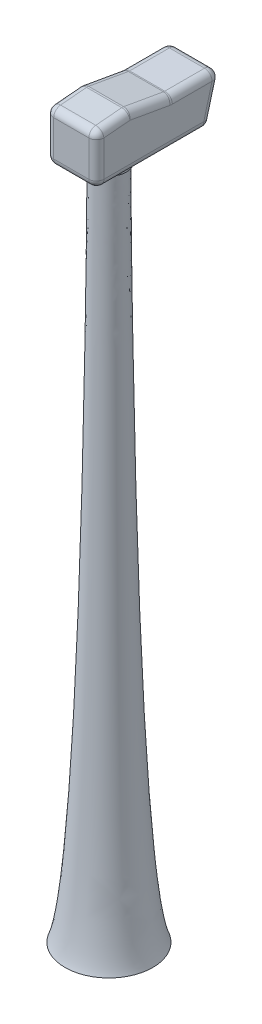
SolidWorks part; units mm, degrees
ref_plane "Ebene vorne" through (0, 0, 0) normal (0, 0, 1) x (1, 0, 0)
ref_plane "Ebene oben" through (0, 0, 0) normal (0, 1, 0) x (1, 0, 0)
ref_plane "Ebene rechts" through (0, 0, 0) normal (1, 0, 0) x (0, 0, -1)
sketch "Skizze2" plane through (0, 0, 0) normal (1, 0, 0) x (0, 0, -1)
  line L0 (2800, -4800) -> (2800, 4800)
  line L1 (-2800, -2400) -> (2800, -2400) construction
  line L2 (-2800, -2400) -> (-2800, 2400) construction
  line L3 (-2800, 2400) -> (2800, 2400) construction
  line L4 (2800, -2400) -> (2800, 2400) construction
  line L5 (-2800, -2400) -> (2800, 2400) construction
  line L6 (-2800, 2400) -> (2800, -2400) construction
  line L7 (2800, 4800) -> (9280, 5366.9265)
  line L8 (9280, 5366.9265) -> (17200, 3970.4169)
  line L9 (17200, 3970.4169) -> (26800, 3970.4169)
  line L10 (26800, 3970.4169) -> (24449.9739, -4800)
  line L11 (24449.9739, -4800) -> (2800, -4800)
  point P0 (0, 0)
  dimension "D1" = 5600
  dimension "D2" = 4800
  dimension "D3" = 95
  dimension "D4" = 165
  dimension "D5" = 75
  dimension "D6" = 6480
  dimension "D7" = 7920
  dimension "D8" = 24000
  dimension "D9" = 2400
  dimension "D10" = 2400
extrude "Aufsatz-Linear austragen1" add sketch "Skizze2" along normal blind 4800 and the other way blind 4800
fillet "Verrundung1" radius 1440 18 edges at (0, -4800, -24449.9739) (-4800, -414.7916, -25624.9869) (-4800, -4800, -13624.9869) (-4800, 0, -2800) (0, -4800, -2800) (4800, 0, -2800) (4800, -414.7916, -25624.9869) (4800, -4800, -13624.9869) (-4800, 3970.4169, -22000) (0, 3970.4169, -26800) (4800, 3970.4169, -22000) (-4800, 4668.6717, -13240) (0, 3970.4169, -17200) (4800, 4668.6717, -13240) (-4800, 5083.4633, -6040) (0, 5366.9265, -9280) (4800, 5083.4633, -6040) (0, 4800, -2800)
sketch "Skizze3" plane through (0, 0, 0) normal (1, 0, 0) x (0, 0, -1)
  line L0 (10000, 0) -> (10000, -215.2925) construction
  line L1 (10000, -3360) -> (6640, -3360)
  line L2 (4240, -3360) -> (23345.023, -3360) construction
  line L3 (6640, -3360) -> (6640, -5760)
  line L4 (6640, -5760) -> (6880, -5760)
  line L5 (6880, -5760) -> (6880, -4800)
  line L6 (23345.023, -4800) -> (4240, -4800) construction
  line L7 (6880, -4800) -> (7024, -4800)
  line L8 (7024, -4800) -> (7024, -5760)
  line L9 (10000, -3360) -> (10000, -135000)
  line L10 (1600, -135000) -> (10000, -135000)
  line L11 (-37.4147, 0) -> (55.262, 0) construction
  line L13 (2800, -3360) -> (2800, 3480.4831) construction
  line L14 (6640, -5760) -> (161.2362, -5760) construction
  spline S0 degree 3 poles (7024, -5760) (7024, -6115.3967) (6652.6696, -122885.6955) (1600, -135000) knots 0 0 0 0 1 1 1 1
  dimension "D1" = 2400
  dimension "D2" = 7200
  dimension "D3" = 3360
  dimension "D4" = 240
  dimension "D5" = 144
  dimension "D6" = 4200
  dimension "D7" = 135000
  dimension "D8" = 81000
  dimension "D9" = 8400
revolve "Rotation1" add sketch "Skizze3" angle 360 about L0
